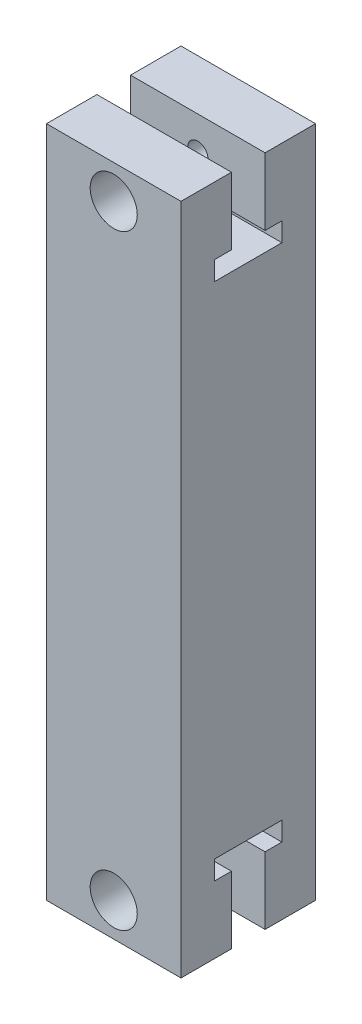
SolidWorks part; units mm, degrees
ref_plane "Front Plane" through (0, 0, 0) normal (0, 0, 1) x (1, 0, 0)
ref_plane "Top Plane" through (0, 0, 0) normal (0, 1, 0) x (1, 0, 0)
ref_plane "Right Plane" through (0, 0, 0) normal (1, 0, 0) x (0, 0, -1)
sketch "Sketch1" plane through (0, 0, 0) normal (0, 1, 0) x (1, 0, 0)
  line L1 (0, 0) -> (20, 0)
  line L2 (0, 0) -> (0, -20)
  line L3 (0, -20) -> (20, -20)
  line L4 (20, 0) -> (20, -20)
extrude "Boss-Extrude1" add sketch "Sketch1" along normal blind 50 and the other way blind 50
sketch "Sketch3" plane through (0, 0, 0) normal (-1, 0, 0) x (0, 0, 1)
  line L1 (7.5, 40) -> (5, 40)
  line L8 (12.5, 40) -> (15, 40)
  line L10 (10, 50) -> (7.5, 50)
  line L11 (15, 40) -> (15, 37.1712)
  line L12 (0, 50) -> (20, 50) construction
  line L13 (10, 50) -> (12.5, 50)
  line L14 (12.5, 50) -> (12.5, 40)
  line L15 (7.5, 50) -> (7.5, 40)
  line L16 (15, 37.1712) -> (5, 37.1712)
  line L17 (5, 37.1712) -> (5, 40)
  line L18 (0, 0) -> (20, 0) construction
  line L30 (20, -50) -> (20, 50) construction
  line L31 (5, -37.1712) -> (5, -40)
  line L32 (15, -37.1712) -> (5, -37.1712)
  line L33 (7.5, -50) -> (7.5, -40)
  line L34 (12.5, -50) -> (12.5, -40)
  line L35 (10, -50) -> (12.5, -50)
  line L36 (15, -40) -> (15, -37.1712)
  line L37 (10, -50) -> (7.5, -50)
  line L38 (12.5, -40) -> (15, -40)
  line L39 (7.5, -40) -> (5, -40)
extrude "Cut-Extrude2" cut sketch "Sketch3" against normal through all
sketch "Sketch4" plane through (0, 0, 0) normal (0, 0, -1) x (-1, 0, 0)
  line L0 (-10, -50) -> (-10, 50) construction
  line L1 (-20, -50) -> (0, -50) construction
  line L2 (-20, 50) -> (0, 50) construction
  line L3 (-20, -40) -> (0, -40) construction
  line L4 (0, -50) -> (-20, -40) construction
  line L5 (-20, -50) -> (0, -40) construction
  line L6 (-20, 40) -> (0, 40) construction
  line L7 (-20, 40) -> (0, 50) construction
  line L8 (-20, 50) -> (0, 40) construction
  circle A0 centre (-10, -45) radius 1.5
  circle A1 centre (-10, 45) radius 1.5
extrude "Cut-Extrude3" cut sketch "Sketch4" against normal through all
sketch "Sketch5" plane through (0, 0, 0) normal (0, 0, -1) x (-1, 0, 0)
  circle A0 centre (-10, -45) radius 3.5
  circle A1 centre (-10, 45) radius 3.5
extrude "Cut-Extrude4" cut sketch "Sketch5" against normal blind 5
sketch "Sketch6" plane through (0, 0, 20) normal (0, 0, 1) x (1, 0, 0)
  circle A0 centre (10, -45) radius 3.5
  circle A1 centre (10, 45) radius 3.5
extrude "Cut-Extrude5" cut sketch "Sketch6" against normal blind 5
